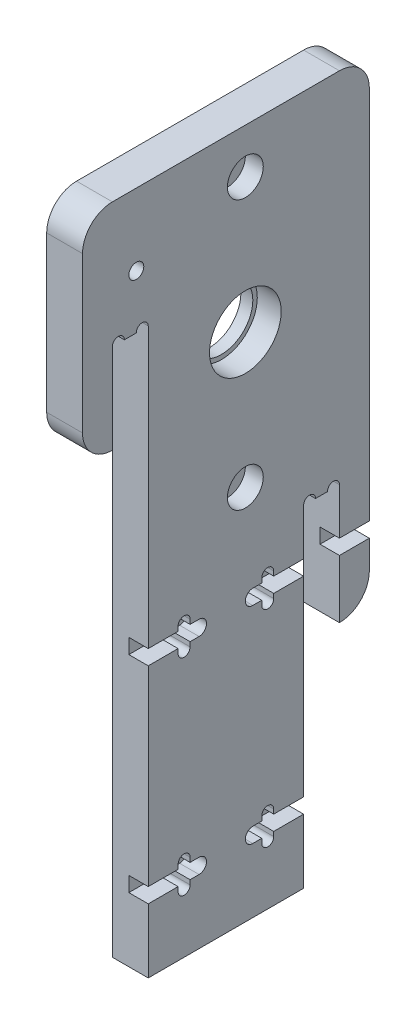
SolidWorks part; units mm, degrees
material "HDPE-green"
ref_plane "Front Plane" through (0, 0, 0) normal (0, 0, 1) x (1, 0, 0)
ref_plane "Top Plane" through (0, 0, 0) normal (0, 1, 0) x (1, 0, 0)
ref_plane "Right Plane" through (0, 0, 0) normal (1, 0, 0) x (0, 0, -1)
sketch "Sketch1" plane through (0, 0, 0) normal (1, 0, 0) x (0, 0, -1)
  line L1 (-31.5, 60) -> (31.5, 60)
  line L2 (-31.5, 60) -> (-31.5, -60)
  line L3 (-31.5, -60) -> (31.5, -60)
  line L4 (31.5, 60) -> (31.5, -60)
  line L5 (-31.5, 60) -> (31.5, -60) construction
  line L6 (-31.5, -60) -> (31.5, 60) construction
  circle A0 centre (0, 0) radius 10.5
  point P0 (0, 0)
  dimension "D3" = 21
  dimension "D1" = 63
  dimension "D2" = 120
extrude "Boss-Extrude1" add sketch "Sketch1" along normal blind 12
sketch "Sketch8" plane through (0, 0, 0) normal (-1, 0, 0) x (0, 0, 1)
  line L2 (44.5, 18) -> (44.5, -12)
  line L3 (44.5, -12) -> (54.5, -12)
  line L4 (54.5, -12) -> (54.5, 60)
  line L5 (54.5, 60) -> (31.5, 60)
  line L7 (31.5, 60) -> (31.5, -60)
  line L9 (31.5, -60) -> (32.5, -60)
  line L10 (32.5, -60) -> (32.5, 18)
  line L11 (32.5, 18) -> (44.5, 18)
  dimension "D1" = 72
  dimension "D2" = 1
  dimension "D3" = 10
  dimension "D4" = 30
  dimension "D5" = 23
extrude "Boss-Extrude2" add sketch "Sketch8" against normal blind 12
sketch "Sketch9" plane through (0, 0, 0) normal (-1, 0, 0) x (0, 0, 1)
  line L0 (-31.5, -60) -> (-31.5, 60) construction
  line L1 (32.5, -60) -> (-19.5, -60)
  line L2 (32.5, -60) -> (32.5, -171)
  line L3 (32.5, -171) -> (-19.5, -171)
  line L4 (-19.5, -60) -> (-19.5, -171)
  dimension "D1" = 12
  dimension "D2" = 111
  dimension "D3" = 52
extrude "Boss-Extrude3" add sketch "Sketch9" against normal blind 12
sketch "Sketch11" plane through (12, 0, 0) normal (1, 0, 0) x (0, 0, -1)
  line L1 (31.5, 60) -> (41.5, 60)
  line L2 (31.5, 60) -> (31.5, -100)
  line L3 (31.5, -100) -> (41.5, -100)
  line L4 (41.5, 60) -> (41.5, -100)
  dimension "D1" = 10
  dimension "D2" = 160
extrude "Boss-Extrude4" add sketch "Sketch11" against normal blind 12
hole_wizard "Ø5.0 (5) Diameter Hole1" positions "Sketch22" profile "Sketch21" hole size "Ø5.0" standard "ISO" end condition up to next
sketch "Sketch22" plane through (12, 0, 0) normal (1, 0, 0) x (0, 0, -1)
  line L1 (41.5, 60) -> (-54.5, 60) construction
  line L2 (-32.5, -171) -> (-32.5, 18) construction
  point P0 (-36.5, 36)
  dimension "D1" = 4
  dimension "D2" = 24
sketch "Sketch21" plane through (12, 36, 36.5) normal (0, 1, 0) x (0, 0, -1)
  line L0 (0, 0) -> (0, 12)
  line L1 (0, 12) -> (2.5, 12)
  line L2 (2.5, 12) -> (2.5, 0)
  line L5 (2.5, 0) -> (0, 0)
  line L11 (0, -6.35) -> (0, 107.95) construction
  dimension "Thru Hole Dia." = 5
  dimension "Thru Hole Depth" = 12
hole_wizard "Linear Rail Mount Hole" positions "Sketch26" profile "Sketch25" legacy end condition up to next
sketch "Sketch26" plane through (12, 0, 0) normal (1, 0, 0) x (0, 0, -1)
  circle A0 centre (0, 0) radius 10.5 construction
  point P1 (0, -45)
  point P3 (0, 45)
  dimension "D1" = 45
  dimension "D2" = 45
sketch "Sketch25" plane through (12, -45, 0) normal (0, 1, 0) x (0, 0, -1)
  line L0 (0, 0) -> (0, 12)
  line L1 (0, 12) -> (2.5, 12)
  line L2 (2.5, 12) -> (2.5, 6)
  line L3 (2.5, 6) -> (6, 6)
  line L4 (6, 6) -> (6, 0)
  line L5 (6, 0) -> (0, 0)
  line L6 (0, 110) -> (0, -10) construction
  dimension "Diameter" = 5
  dimension "Depth" = 12
  dimension "C-Bore Diameter" = 12
  dimension "C-Bore Depth" = 6
sketch "Sketch27" plane through (12, 0, 0) normal (1, 0, 0) x (0, 0, -1)
  circle A0 centre (0, 0) radius 12
  dimension "D1" = 24
extrude "Cut-Extrude1" cut sketch "Sketch27" against normal blind 8
sketch "Sketch28" plane through (12, 0, 0) normal (1, 0, 0) x (0, 0, -1)
  line L0 (19.5, -60) -> (31.5, -60) construction
  line L1 (-32.5, 18) -> (-44.5, 18) construction
  line L2 (-44.5, 18) -> (-40.5, 18)
  line L3 (-36.5, 18) -> (-32.5, 18)
  line L4 (19.5, -60) -> (23.5, -60)
  line L5 (27.5, -60) -> (31.5, -60)
  arc A0 (19.5, -60) -> (23.5, -60) centre (21.5, -60) cw
  arc A1 (31.5, -60) -> (27.5, -60) centre (29.5, -60) ccw
  arc A2 (-44.5, 18) -> (-40.5, 18) centre (-42.5, 18) cw
  arc A3 (-32.5, 18) -> (-36.5, 18) centre (-34.5, 18) ccw
  dimension "D1" = 2
  dimension "D2" = 2
  dimension "D3" = 2
  dimension "D4" = 2
extrude "Cut-Extrude2" cut sketch "Sketch28" against normal up to next
fillet "Fillet1" radius 10 4 edges at (6, -12, 54.5) (6, -100, -41.5) (6, 60, 54.5) (6, 60, -41.5)
sketch "Sketch29" plane through (12, 0, 0) normal (1, 0, 0) x (0, 0, -1)
  line L0 (7.5, -143) -> (7.5, -151) construction
  line L1 (9.5, -143) -> (9.5, -151)
  line L2 (5.5, -143) -> (5.5, -151)
  line L3 (19.5, -60) -> (19.5, -171) construction
  line L4 (19.5, -171) -> (-32.5, -171) construction
  arc A0 (9.5, -143) -> (5.5, -143) centre (7.5, -143) ccw
  arc A1 (5.5, -151) -> (9.5, -151) centre (7.5, -151) ccw
  point P2 (7.5, -147)
  dimension "D1" = 8
  dimension "D2" = 2
  dimension "D3" = 12
  dimension "D4" = 24
extrude "Cut-Extrude3" cut sketch "Sketch29" against normal blind 8
sketch "Sketch31" plane through (12, 0, 0) normal (1, 0, 0) x (0, 0, -1)
  line L0 (65.3975, -147) -> (2.5, -147) construction
  line L1 (65.3975, -149.5) -> (2.5, -149.5)
  line L2 (65.3975, -144.5) -> (2.5, -144.5)
  line L3 (19.5, -60) -> (19.5, -171) construction
  line L4 (19.5, -171) -> (-32.5, -171) construction
  arc A0 (65.3975, -149.5) -> (65.3975, -144.5) centre (65.3975, -147) ccw
  arc A1 (2.5, -144.5) -> (2.5, -149.5) centre (2.5, -147) ccw
  point P2 (33.9487, -147)
  dimension "D1" = 17
  dimension "D2" = 2.5
  dimension "D3" = 24
extrude "Cut-Extrude4" cut sketch "Sketch31" against normal blind 6.5
pattern_linear "LPattern1" count 2 spacing 69 along (0, 1, 0) of "Cut-Extrude4", "Cut-Extrude3"
ref_plane "Plane1" through (0, 0, 6.5) normal (0, 0, -1) x (-1, 0, 0)
mirror "Mirror1" about plane through (0, 0, 6.5) normal (0, 0, -1) of "LPattern1", "Cut-Extrude3", "Cut-Extrude4"
